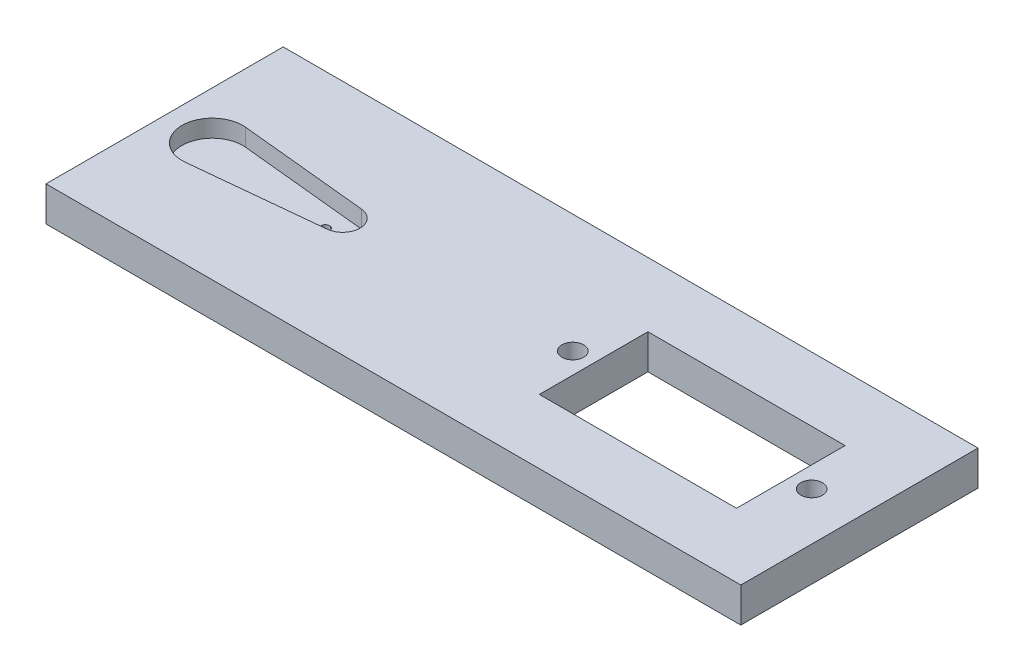
SolidWorks part; units mm, degrees
ref_plane "前视基准面" through (0, 0, 0) normal (0, 0, 1) x (1, 0, 0)
ref_plane "上视基准面" through (0, 0, 0) normal (0, 1, 0) x (1, 0, 0)
ref_plane "右视基准面" through (0, 0, 0) normal (1, 0, 0) x (0, 0, -1)
other "Configuration Table"
sketch "草图1" plane through (0, 0, 0) normal (0, 1, 0) x (1, 0, 0)
  line L0 (-34.15, 3.4825) -> (-19.3, 1.99)
  line L1 (-40, 13.6546) -> (40, 13.6546)
  line L2 (-40, 13.6546) -> (-40, -13.6546)
  line L3 (-40, -13.6546) -> (40, -13.6546)
  line L4 (40, 13.6546) -> (40, -13.6546)
  line L5 (-40, 13.6546) -> (40, -13.6546) construction
  line L6 (-40, -13.6546) -> (40, 13.6546) construction
  line L7 (9.4, 6.25) -> (32.1, 6.25)
  line L8 (9.4, 6.25) -> (9.4, -6.25)
  line L9 (9.4, -6.25) -> (32.1, -6.25)
  line L10 (32.1, 6.25) -> (32.1, -6.25)
  line L11 (9.4, 6.25) -> (32.1, -6.25) construction
  line L12 (9.4, -6.25) -> (32.1, 6.25) construction
  line L13 (-34.15, -3.4825) -> (-19.3, -1.99)
  line L14 (20.75, -8.5449) -> (20.75, 8.614) construction
  circle A0 centre (-34.5, 0) radius 3.5
  circle A1 centre (-21.5, 0) radius 0.5
  circle A2 centre (-19.5, 0) radius 2
  circle A3 centre (7, 0) radius 1.25
  circle A4 centre (34.5, 0) radius 1.25
  point P0 (0, 0)
  point P12 (20.75, 0)
  point P21 (-40, 0)
  point P31 (40, 0)
  dimension "D1" = 7
  dimension "D2" = 4
  dimension "D3" = 1
  dimension "D5" = 13
  dimension "D6" = 5.5
  dimension "D8" = 12.5
  dimension "D9" = 17.1589
  dimension "D10" = 27.5
  dimension "D11" = 5.5
  dimension "D12" = 2.5
  dimension "D13" = 27.3092
  dimension "D4" = 15
  dimension "D7" = 22.7
  dimension "D14" = 80
extrude "凸台-拉伸2" add sketch "草图1" along normal blind 4 contours L4 L1 L2 L3 A4 A3 A2 L13 A0 L0 L7 L10 L9 L8 region at (-1.6754, 0, 0)
extrude "凸台-拉伸3" add sketch "草图1<4>" along normal blind 2 contours A0 | A2 L0 A0 L13 A1 | A2 A1 region at (-26.7322, 0, 0) region at (-34.5, 0, 0) region at (-19.4458, 0, 0)
sketch "草图1<4>" plane through (0, 0, 0) normal (0, 1, 0) x (1, 0, 0) same geometry as "草图1"
